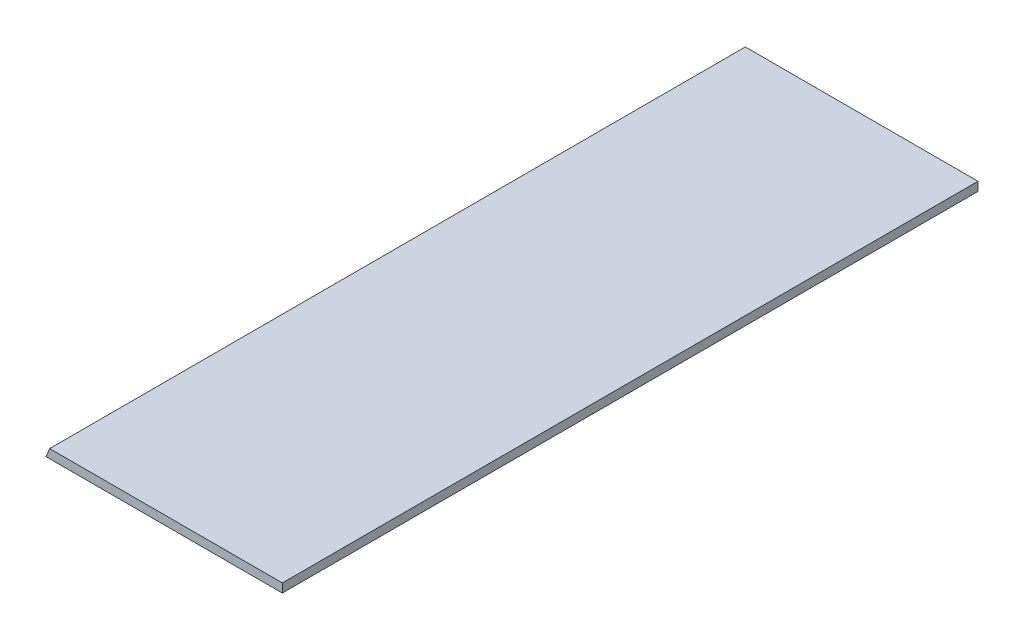
SolidWorks part; units mm, degrees
ref_plane "Front Plane" through (0, 0, 0) normal (0, 0, 1) x (1, 0, 0)
ref_plane "Top Plane" through (0, 0, 0) normal (0, 1, 0) x (1, 0, 0)
ref_plane "Right Plane" through (0, 0, 0) normal (1, 0, 0) x (0, 0, -1)
sketch "Sketch1" plane through (0, 0, 0) normal (0, 0, 1) x (1, 0, 0)
  line L0 (0, 0) -> (2.6303, 6.35)
  line L1 (2.6303, 6.35) -> (170.434, 6.35)
  line L2 (170.434, 6.35) -> (170.434, 0)
  line L3 (170.434, 0) -> (0, 0)
  dimension "D1" = 67.5
  dimension "D2" = 6.35
  dimension "D3" = 170.434
extrude "Boss-Extrude1" add sketch "Sketch1" along normal blind 501.65
